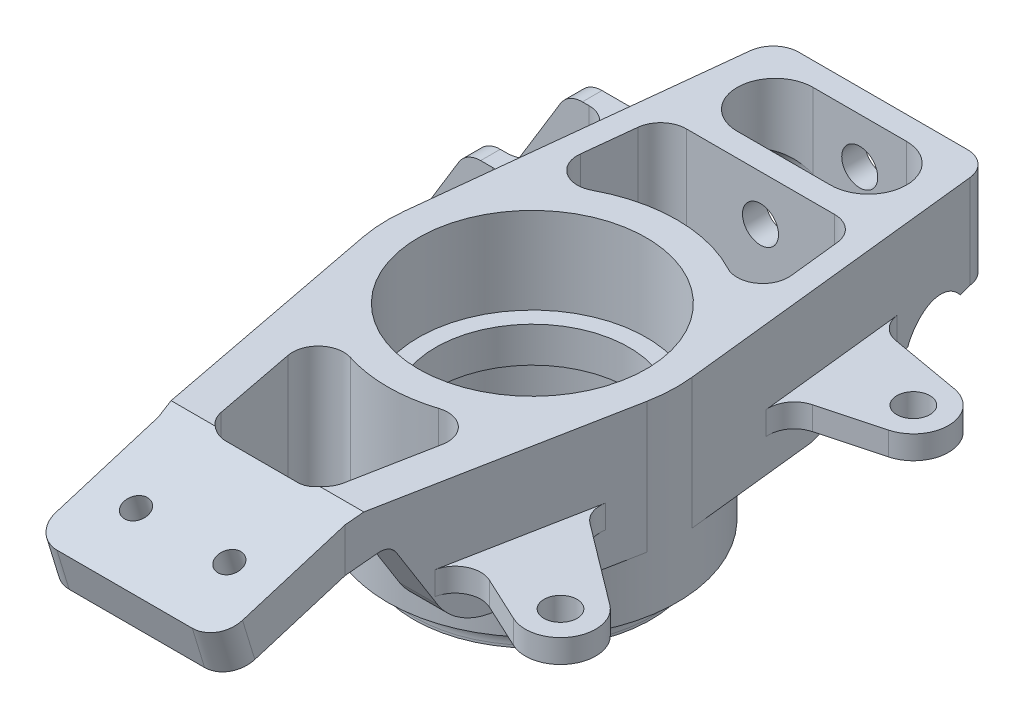
SolidWorks part; units mm, degrees
material "6061-T6 (SS)"
ref_plane "Front Plane" through (0, 0, 0) normal (0, 0, 1) x (1, 0, 0)
ref_plane "Top Plane" through (0, 0, 0) normal (0, 1, 0) x (1, 0, 0)
ref_plane "Right Plane" through (0, 0, 0) normal (1, 0, 0) x (0, 0, -1)
sketch "UBJ LBJ Geometry" plane through (0, 0, 0) normal (1, 0, 0) x (0, 0, -1)
  line L0 (0, 0) -> (0, -97.4059) construction
  line L1 (0, 0) -> (-30.7529, 0) construction
  line L2 (0, 22) -> (-45.5659, 22) construction
  line L3 (0, -10.5425) -> (-23.1063, -10.5425) construction
  line L4 (-84.7344, -51.66) -> (78.74, -22.958) construction
  line L5 (49.4563, 0) -> (49.4563, -88.2735) construction
  circle A0 centre (-84.7344, -51.66) radius 10.3251 construction
  circle A1 centre (78.74, -22.958) radius 10.3251 construction
  dimension "D7" = 20.6502
  dimension "D8" = 20.6502
  dimension "D1" = 22
  dimension "D2" = 32.5425
  dimension "D3" = 44.958
  dimension "D4" = 73.66
  dimension "D5" = 84.7344
  dimension "D6" = 78.74
  dimension "D9" = 29.2837
ref_plane "Wheel Face " through (0, 22, 0) normal (0, -1, 0) x (-1, 0, 0)
ref_plane "Upright Face" through (0, -10.5425, 0) normal (0, -1, 0) x (-1, 0, 0)
ref_plane "Tie Bracket Plane" through (0, 0, -49.4563) normal (0, 0, 1) x (1, 0, 0)
sketch "Tie Bracket Geometry" plane through (0, 0, -49.4563) normal (0, 0, 1) x (1, 0, 0)
  line L0 (0, -28.0995) -> (-60.5599, -51.7108) construction
  line L4 (0, 200000) -> (0, -200097.4059) construction
  circle A0 centre (-60.5599, -51.7108) radius 8.948 construction
  dimension "D1" = 65
  dimension "D2" = 68.7
sketch "Sketch1" plane through (0, 0, 0) normal (0, 0, 1) x (1, 0, 0)
  line L1 (-75.0953, -10.5425) -> (75.0953, -10.5425) construction
  line L2 (-39.37, -10.5425) -> (-39.37, -61.3425)
  line L3 (-39.37, -61.3425) -> (-32.258, -61.3425)
  line L4 (-32.258, -61.3425) -> (-32.258, -68.9625)
  line L5 (-32.258, -68.9625) -> (-30.9829, -68.9625)
  line L8 (-30.9829, -10.5425) -> (-30.9829, -34.0375)
  line L9 (-30.9829, -34.0375) -> (-26.289, -34.0375)
  line L10 (-26.289, -34.0375) -> (-26.289, -43.6895)
  line L11 (-26.289, -43.6895) -> (-30.9829, -43.6895)
  line L12 (-30.9829, -43.6895) -> (-30.9829, -68.9625)
  line L15 (-39.37, -10.5425) -> (-30.9829, -10.5425)
  line L17 (0, 0) -> (0, -23.5057) construction
  dimension "D1" = 9.652
  dimension "D2" = 61.9658
  dimension "D3" = 25.273
  dimension "D4" = 52.578
  dimension "D5" = 23.495
  dimension "D6" = 50.8
  dimension "D7" = 78.74
  dimension "D8" = 64.516
revolve "Bearing Housing Revolve" add sketch "Sketch1" angle 360 about L17
fillet "Bearing Housing Fillet" radius 6.985 1 edges at (0, -61.3425, 32.258)
sketch "Sketch2" plane through (0, -10.5425, 0) normal (0, -1, 0) x (-1, 0, 0)
  line L3 (39.37, -43.18) -> (39.37, 0)
  line L4 (-39.37, -43.18) -> (-39.37, 0)
  line L5 (39.37, -43.18) -> (-39.37, -43.18)
  circle A4 centre (0, 0) radius 39.37 construction
  arc A5 (39.37, 0) -> (-39.37, 0) centre (0, 0) cw
  dimension "D1" = 43.18
extrude "UBJ Prep" add sketch "Sketch2" along normal blind 35.56
sketch "Sketch3" plane through (-39.37, 0, 0) normal (-1, 0, 0) x (0, 0, 1)
  line L0 (-120.7672, 22) -> (120.7672, 22) construction
  line L1 (43.18, -10.5425) -> (72.0727, -10.5425)
  line L2 (72.0727, -10.5425) -> (110.937, -22.4245)
  line L3 (110.937, -22.4245) -> (107.5952, -33.355)
  line L4 (107.5952, -33.355) -> (68.7309, -21.473)
  line L6 (43.18, -46.1025) -> (43.18, -10.5425)
  line L7 (72.0727, -10.5425) -> (68.7309, -21.473) construction
  line L8 (104.3241, 12.415) -> (84.7344, -51.66) construction
  line L9 (55.2328, -39.1959) -> (64.6966, -23.0471)
  circle A0 centre (84.7344, -51.66) radius 12.7 construction
  arc A1 (43.18, -46.1025) -> (55.2328, -39.1959) centre (43.18, -32.1325) ccw
  arc A2 (68.7309, -21.473) -> (64.6966, -23.0471) centre (67.7098, -24.8129) ccw
  dimension "D7" = 6.985
  dimension "D8" = 27.94
  dimension "D9" = 25.4
  dimension "D1" = 73.66
  dimension "D2" = 84.7344
  dimension "D3" = 11.43
  dimension "D4" = 40.64
  dimension "D5" = 17
  dimension "D6" = 16.51
extrude "UBJ Extrude " add sketch "Sketch3" against normal up to surface (78.74 mm away) up to face at (39.37, -28.3225, 21.59)
sketch "Sketch4" plane through (0, -0.4206, -0.1286) normal (0, -0.9563, -0.2924) x (1, 0, 0)
  line L0 (0, 112.6458) -> (0, 27.8969) construction
  line L1 (39.37, 112.6458) -> (-39.37, 112.6458) construction
  line L3 (-12.7, 96.1358) -> (12.7, 96.1358) construction
  circle A0 centre (-12.7, 96.1358) radius 3.2639
  circle A1 centre (12.7, 96.1358) radius 3.2639
  point P8 (0, 96.1358)
  dimension "D2" = 6.5278
  dimension "D1" = 25.4
extrude "Camber Block Holes" cut sketch "Sketch4" against normal up to surface (11.43 mm away) up to face at (0, -16.4835, 91.5049)
sketch "Sketch5" plane through (0, -46.1025, 0) normal (0, -1, 0) x (1, 0, 0)
  line L0 (-25.4, 107.5952) -> (-25.4, 76.3532)
  line L1 (25.4, 110.937) -> (39.37, 110.937)
  line L2 (39.37, 107.5952) -> (-39.37, 107.5952) construction
  line L4 (-25.4, 76.3532) -> (-38.6608, 7.4393)
  line L5 (25.4, 107.5952) -> (25.4, 76.3532)
  line L6 (25.4, 76.3532) -> (38.6608, 7.4393)
  line L7 (-25.4, 107.5952) -> (-25.4, 110.937)
  line L8 (39.37, 110.937) -> (-39.37, 110.937) construction
  line L9 (25.4, 107.5952) -> (25.4, 110.937)
  line L10 (-25.4, 110.937) -> (-39.37, 110.937)
  line L11 (-39.37, 110.937) -> (-39.37, 0)
  line L12 (39.37, 110.937) -> (39.37, 0)
  line L13 (-15.5718, 73.66) -> (15.5718, 73.66)
  line L14 (-15.5718, 73.66) -> (-23.6959, 31.4404)
  line L15 (15.5718, 73.66) -> (23.6959, 31.4404)
  arc A0 (-39.37, 0) -> (-38.6608, 7.4393) centre (0, 0) cw
  circle A1 centre (0, 0) radius 39.37 construction
  arc A2 (39.37, 0) -> (-39.37, 0) centre (0, 0) ccw construction
  arc A3 (39.37, 0) -> (38.6608, 7.4393) centre (0, 0) ccw
  arc A4 (-23.6959, 31.4404) -> (23.6959, 31.4404) centre (0, 0) cw
  point P31 (0, 73.66)
  dimension "D1" = 25.4
  dimension "D2" = 10.16
  dimension "D3" = 31.242
  dimension "D4" = 73.66
extrude "Weight Saving" cut sketch "Sketch5" against normal through all
fillet "Fillet2" radius 6.985 4 edges at (23.6959, -28.3225, 31.4404) (-23.6959, -28.3225, 31.4404) (15.5718, -17.0039, 73.66) (-15.5718, -17.0039, 73.66)
sketch "Sketch6" plane through (0, -10.5425, 0) normal (0, -1, 0) x (-1, 0, 0)
  line L0 (-39.37, 0) -> (-39.37, 40.64)
  line L1 (-39.37, 40.64) -> (39.37, 40.64)
  line L2 (39.37, 40.64) -> (39.37, 0)
  circle A0 centre (0, 0) radius 39.37 construction
  arc A1 (-39.37, 0) -> (39.37, 0) centre (0, 0) cw
  dimension "D1" = 40.64
extrude "LBJ Prep" add sketch "Sketch6" along normal blind 35.56
sketch "Sketch8" plane through (-39.37, 0, 0) normal (-1, 0, 0) x (0, 0, 1)
  line L0 (-40.64, -10.5425) -> (-95.4151, -10.5425)
  line L1 (-95.4151, -10.5425) -> (-95.4151, -35.9425)
  line L2 (-95.4151, -35.9425) -> (-89.0651, -35.9425)
  line L7 (-40.64, -46.1025) -> (-40.64, -10.5425)
  line L8 (-120.7672, 22) -> (120.7672, 22) construction
  line L9 (-89.0651, -35.9425) -> (-89.0651, -10.5425) construction
  line L10 (-89.0651, -35.9425) -> (-40.64, -46.1025)
  circle A0 centre (-78.74, -22.958) radius 10.3251 construction
  dimension "D3" = 20.6502
  dimension "D1" = 78.74
  dimension "D2" = 44.958
  dimension "D4" = 6.35
  dimension "D5" = 25.4
extrude "LBJ Area " add sketch "Sketch8" against normal up to surface (78.74 mm away) up to face at (39.37, -28.3225, -20.32)
sketch "Sketch7" plane through (0, -46.1025, 0) normal (0, -1, 0) x (1, 0, 0)
  line L0 (-12.7, -78.74) -> (12.7, -78.74) construction
  line L1 (0, -200000) -> (0, 200045.5659) construction
  line L2 (-12.7, -68.4149) -> (12.7, -68.4149)
  line L3 (-12.7, -89.0651) -> (12.7, -89.0651)
  line L4 (-29.21, -95.4151) -> (-39.1385, -4.2631)
  line L5 (39.37, -95.4151) -> (-39.37, -95.4151) construction
  line L6 (29.21, -95.4151) -> (39.1385, -4.2631)
  line L7 (-29.21, -95.4151) -> (-39.37, -95.4151)
  line L8 (-39.37, -95.4151) -> (-39.37, 0)
  line L9 (29.21, -95.4151) -> (39.37, -95.4151)
  line L10 (39.37, -95.4151) -> (39.37, 0)
  line L13 (-26.455, -62.0649) -> (26.455, -62.0649)
  line L14 (26.455, -62.0649) -> (30.5043, -24.8895)
  line L15 (-26.455, -62.0649) -> (-30.5043, -24.8895)
  arc A0 (-12.7, -68.4149) -> (-12.7, -89.0651) centre (-12.7, -78.74) ccw
  arc A1 (12.7, -89.0651) -> (12.7, -68.4149) centre (12.7, -78.74) ccw
  circle A2 centre (0, 0) radius 39.37 construction
  arc A3 (-39.37, 0) -> (39.37, 0) centre (0, 0) ccw construction
  arc A4 (39.37, 0) -> (39.1385, -4.2631) centre (0, 0) cw
  arc A5 (-39.37, 0) -> (-39.1385, -4.2631) centre (0, 0) ccw
  arc A6 (-30.5043, -24.8895) -> (30.5043, -24.8895) centre (0, 0) ccw
  point P4 (0, -78.74)
  point P28 (0, -62.0649)
  dimension "D1" = 78.74
  dimension "D2" = 20.6502
  dimension "D3" = 25.4
  dimension "D4" = 10.16
  dimension "D5" = 6.35
  dimension "D6" = 6.35
extrude "LBJ Taper And Slot" cut sketch "Sketch7" against normal up to surface (35.56 mm away)
fillet "Fillet3" radius 6.985 4 edges at (26.455, -26.0749, -62.0649) (-26.455, -26.0749, -62.0649) (30.5043, -28.3225, -24.8895) (-30.5043, -28.3225, -24.8895)
extrude "LBJ Holes 3/8 Close Fit Hole" cut sketch "Sketch9" against normal up to surface (33.3502 mm away) up to face at (0, -26.0749, -62.0649)
sketch "Sketch9" plane through (0, 0, -95.4151) normal (0, 0, -1) x (-1, 0, 0)
  circle A0 centre (0, -22.958) radius 4.9022
  dimension "D2" = 9.8044
  dimension "D1" = 22.958
ref_plane "Brake Mounting Plane" through (0, -30.7025, 0) normal (0, 1, 0) x (1, 0, 0)
sketch "Sketch10" plane through (0, -30.7025, 0) normal (0, 1, 0) x (1, 0, 0)
  line L0 (87.9814, 0) -> (161.3053, 0) construction
  line L1 (0, 72.9505) -> (0, 47.1638) construction
  line L2 (55.6514, 48) -> (55.6514, -48) construction
  line L3 (58.1309, 38.7464) -> (36.0276, 32.8239)
  line L4 (39.1385, 4.2631) -> (29.21, 95.4151) construction
  line L5 (36.0276, 32.8239) -> (32.8776, 61.7434)
  line L6 (32.8776, 61.7434) -> (57.3149, 57.4345)
  line L7 (61.4168, -40.3491) -> (36.0119, -21.2051)
  line L8 (26.2237, -72.0727) -> (38.6608, -7.4393) construction
  line L9 (36.0119, -21.2051) -> (31.031, -47.0897)
  line L10 (31.031, -47.0897) -> (51.6027, -56.6824)
  circle A0 centre (55.6514, 48) radius 4.5
  circle A1 centre (55.6514, -48) radius 4.5
  arc A2 (51.6027, -56.6824) -> (61.4168, -40.3491) centre (55.6514, -48) ccw
  arc A3 (58.1309, 38.7464) -> (57.3149, 57.4345) centre (55.6514, 48) ccw
  point P7 (55.6514, 0)
  dimension "D2" = 9
  dimension "D3" = 5.08
  dimension "D4" = 5.08
  dimension "D1" = 96
  dimension "D5" = 55.6514
  dimension "D6" = 80
  dimension "D7" = 75
  dimension "D8" = 53
  dimension "D9" = 65
extrude "Brake Mounts" add sketch "Sketch10" against normal blind 6.35
fillet "Fillet4" radius 6.985 4 edges at (36.0119, -33.8775, 21.2051) (31.031, -33.8775, 47.0897) (36.0276, -33.8775, -32.8239) (32.8776, -33.8775, -61.7434)
sketch "Sketch17" plane through (0, -37.0525, 0) normal (0, -1, 0) x (1, 0, 0)
  line L1 (36.8349, 16.928) -> (29.3384, 55.8861) construction
  line L3 (32.3099, -66.9555) -> (36.6761, -26.8705) construction
  line L6 (57.3149, -57.4345) -> (38.0409, -60.833) construction
  line L12 (61.4168, 40.3491) -> (39.4904, 23.8263) construction
  circle A0 centre (40.1682, 38.2515) radius 4.7625
  circle A1 centre (41.7635, -47.6031) radius 4.7625
  dimension "D1" = 9.525
  dimension "D2" = 9.525
  dimension "D3" = 2.54
  dimension "D4" = 2.54
  dimension "D5" = 7.62
  dimension "D6" = 6.35
extrude "rotor Cut " [suppressed] cut sketch "Sketch17" against normal up to surface (6.35 mm away)
sketch "Sketch16" plane through (0, -46.1025, 0) normal (0, 1, 0) x (1, 0, 0)
  line L0 (-38.6345, 8.89) -> (-55.7371, 8.89)
  line L1 (-38.6608, -7.4393) -> (-26.2237, -72.0727) construction
  line L2 (-55.7371, 8.89) -> (-55.7371, -8.89)
  line L3 (-55.7371, -8.89) -> (-38.3816, -8.89)
  line L5 (-29.21, 95.4151) -> (-39.1385, 4.2631) construction
  line L6 (-38.6345, 8.89) -> (-38.3816, -8.89)
  circle A0 centre (-46.609, 0) radius 5.9531
  point P8 (-55.7371, 0)
  dimension "D1" = 3.175
  dimension "D3" = 11.9062
  dimension "D2" = 46.609
  dimension "D4" = 17.78
extrude "Speed Sensor Mount" add sketch "Sketch16" along normal blind 5.08
fillet "Speed Sensor Fillet" radius 6.985 4 edges at (-55.7371, -43.5625, 8.89) (-55.7371, -43.5625, -8.89) (-38.3816, -43.5625, 8.89) (-38.6345, -43.5625, -8.89)
thread "15/32-32" pitch 0.9071 method cut profile "Thread Profile1" start angle 0, offset 1, length 10, pitch 0.7937, diameter 11.9062
ref_plane "Plane1" through (-40.6559, -45.1025, 0) normal (0, 0, 1) x (1, 0, 0)
sketch "Thread Profile1" plane through (-40.6559, -45.1025, 0) normal (0, 0, 1) x (1, 0, 0)
  line L0 (0, 0) -> (0, 0.9071) construction
  line L1 (0, 0) -> (0.491, 0.2835)
  line L2 (0.491, 0.2835) -> (0.491, 0.3969)
  line L3 (0.491, 0.3969) -> (0, 0.6804)
  line L4 (0.491, 0.3402) -> (0, 0.3402) construction
  line L11 (0, 0) -> (0, 0.6804)
  point P2 (0, 0)
  dimension "Pitch" = 0.9071
  dimension "Profile_Angle" = 60
  dimension "Profile_Land" = 0.1134
  dimension "Profile_Height" = 0.491
sketch "Sketch12" plane through (0, 0, -49.4563) normal (0, 0, 1) x (1, 0, 0)
  line L0 (0, 3.2946) -> (0, -38.5659) construction
  line L1 (-90.5661, 0) -> (-38.2005, 0) construction
  line L2 (-68.726, -10.5425) -> (-68.726, -51.7108)
  line L3 (-52.3938, -10.5425) -> (-52.3938, -51.7108)
  line L4 (-68.726, -10.5425) -> (-52.3938, -10.5425)
  line L6 (-75.0953, -10.5425) -> (75.0953, -10.5425) construction
  circle A0 centre (-60.5599, -51.7108) radius 3.2639
  arc A1 (-68.726, -51.7108) -> (-52.3938, -51.7108) centre (-60.5599, -51.7108) ccw
  dimension "D1" = 6.5278
  dimension "D2" = 4.9022
extrude "Initial Toe Bracket" add sketch "Sketch12" along normal blind 16.51 and the other way blind 16.51 separate body
sketch "Sketch13" plane through (-52.3938, 0, 0) normal (1, 0, 0) x (0, 0, -1)
  line L0 (32.9463, -16.8925) -> (65.9663, -16.8925)
  line L1 (65.9663, -51.7108) -> (65.9663, -10.5425) construction
  line L2 (65.9663, -16.8925) -> (65.9663, -38.4825)
  line L3 (32.9463, -16.8925) -> (32.9463, -38.4825)
  line L4 (200000, -10.5425) -> (-200023.1063, -10.5425) construction
  line L5 (32.9463, -38.4825) -> (65.9663, -38.4825)
  line L6 (32.9463, -51.7108) -> (32.9463, -10.5425) construction
  dimension "D1" = 6.35
  dimension "D2" = 21.59
extrude "Toe Bracket Connection to Upright" add sketch "Sketch13" along normal up to surface (19.9762 mm away) up to face at (-34.7109, -33.4025, -44.9123)
sketch "Sketch14" plane through (0, 0, -65.9663) normal (0, 0, -1) x (-1, 0, 0)
  line L0 (52.3938, -16.8925) -> (68.726, -16.8925)
  line L1 (68.726, -10.5425) -> (68.726, -51.7108) construction
  line L2 (68.726, -16.8925) -> (68.726, -10.5425)
  line L3 (68.726, -10.5425) -> (52.3938, -10.5425)
  line L4 (52.3938, -10.5425) -> (52.3938, -16.8925)
extrude "Excess Toe Bracket Cut" cut sketch "Sketch14" against normal up to surface (33.02 mm away) up to face at (-52.382, -30.4278, -32.9463)
sketch "Sketch19" plane through (0, 0, -32.9463) normal (0, 0, 1) x (1, 0, 0)
  line L0 (-53.5754, -55.9418) -> (-42.9993, -38.4825)
  line L1 (-42.9993, -38.4825) -> (-52.3938, -38.4825)
  line L2 (-52.3938, -38.4825) -> (-53.5754, -55.9418)
  line L3 (-36.0143, -38.4825) -> (-52.3938, -38.4825) construction
  line L4 (-36.0143, -16.8925) -> (-36.0143, -38.4825) construction
  arc A0 (-68.726, -51.7108) -> (-52.3938, -51.7108) centre (-60.5599, -51.7108) ccw construction
  dimension "D1" = 6.985
extrude "Adding To Toe" add sketch "Sketch19" against normal up to surface (33.02 mm away) up to face at (-51.1792, -37.0563, -65.9663)
sketch "Sketch20" plane through (0, 0, -32.9463) normal (0, 0, 1) x (1, 0, 0)
  line L0 (-50.946, -16.8925) -> (-68.726, -16.8925)
  line L1 (-36.0143, -16.8925) -> (-68.726, -16.8925) construction
  line L2 (-68.726, -16.8925) -> (-68.726, -46.1025)
  line L3 (-68.726, -16.8925) -> (-68.726, -51.7108) construction
  line L4 (-68.726, -46.1025) -> (-50.946, -16.8925)
  dimension "D1" = 17.78
  dimension "D2" = 29.21
extrude "Cut-Extrude1" cut sketch "Sketch20" against normal up to surface (33.02 mm away) up to face at (-50.0779, -37.3587, -65.9663)
sketch "Sketch15" plane through (-68.726, 0, 0) normal (-1, 0, 0) x (0, 0, 1)
  line L0 (-60.6323, -16.8925) -> (-38.2803, -16.8925)
  line L1 (-38.2803, -16.8925) -> (-38.2803, -59.8769)
  line L2 (-65.9663, -59.8769) -> (-32.9463, -59.8769) construction
  line L3 (-38.2803, -59.8769) -> (-60.6323, -59.8769)
  line L4 (-60.6323, -59.8769) -> (-60.6323, -16.8925)
  line L6 (-49.4563, -25.7825) -> (-49.4563, -39.109) construction
  line L8 (-32.9463, -16.8925) -> (-65.9663, -16.8925) construction
  point P9 (-49.4563, -16.8925)
  point P11 (-49.4563, -16.8925)
  dimension "D1" = 22.352
extrude "Toe Bracket Slot" cut sketch "Sketch15" against normal blind 30.48
fillet "Toe Bracket Fillet" radius 6.985 2 edges at (-32.4176, -27.6875, -65.9663) (-36.0143, -27.6875, -32.9463)
fillet "Fillet7" radius 6.985 4 edges at (-68.726, -46.1025, -35.6133) (-68.726, -46.1025, -63.2993) (-50.946, -16.8925, -63.2993) (-50.946, -16.8925, -35.6133)
fillet "Inside Toe Fillet" radius 6.985 2 edges at (-38.246, -27.6875, -38.2803) (-38.246, -27.6875, -60.6323)
fillet "Outside Fillets" radius 6.985 4 edges at (-25.4, -27.8897, 109.2661) (25.4, -27.8897, 109.2661) (29.21, -23.2425, -95.4151) (-29.21, -23.2425, -95.4151)
sketch "Angle Reference" plane through (0, 0, -95.4151) normal (0, 0, -1) x (-1, 0, 0)
  line L0 (0, -22.958) -> (32.5253, -73.0426) construction
  line L1 (0, 0) -> (0, -88.2735) construction
  line L2 (0, -22.958) -> (69.6053, -82.0294) construction
  dimension "D1" = 33
  dimension "D2" = 16.68
ref_plane "Plane2" through (0, -22.958, -78.74) normal (-0.7624, -0.6471, 0) x (0, 0, 1)
sketch "Sketch22" plane through (0, -22.958, -78.74) normal (-0.7624, -0.6471, 0) x (0, 0, 1)
  line L0 (0, 2.032) -> (0, -5.588) construction
  line L3 (10.3251, 2.032) -> (10.3251, -5.588)
  line L4 (-10.3251, 2.032) -> (-10.3251, -5.588)
  arc A2 (10.3251, 2.032) -> (-10.3251, 2.032) centre (0, 2.032) ccw
  arc A3 (-10.3251, -5.588) -> (10.3251, -5.588) centre (0, -5.588) ccw
  point P2 (0, -1.778)
  dimension "D1" = 20.6502
  dimension "D2" = 2.032
  dimension "D3" = 7.62
extrude "Angle Slot Cut" cut sketch "Sketch22" along normal through all
mirror "Mirror1" about plane through (0, 0, 0) normal (1, 0, 0) of "Angle Slot Cut"
equation "\"Wheel_Offset\"= 22mm"
equation "\"HUB_to_UBJ_Lat\"= 2.9in"
equation "\"Hub_to_UBJ_Vert\"= 3.336in"
equation "\"Hub_to_LBJ_Lat\"= 1.77in"
equation "\"Hub_to_LBJ_Vert\"= 3.1in"
equation "\"Wheel_face_to_Upright_back\"= 1.2812in'This is the distance between the whee face to the upright back."
equation "\"UBJ_Angle\"= 17deg"
equation "\"D2@UBJ LBJ Geometry\" = \"Wheel_face_to_Upright_back\""
equation "\"D3@UBJ LBJ Geometry\" = \"Hub_to_LBJ_Lat\""
equation "\"D4@UBJ LBJ Geometry\" = \"HUB_to_UBJ_Lat\""
equation "\"D5@UBJ LBJ Geometry\" = \"Hub_to_UBJ_Vert\""
equation "\"D6@UBJ LBJ Geometry\" = \"Hub_to_LBJ_Vert\""
equation "\"D1@Sketch3\"=\"HUB_to_UBJ_Lat\""
equation "\"D2@Sketch3\"=\"Hub_to_UBJ_Vert\""
equation "\"D1@Sketch8\"=\"Hub_to_LBJ_Vert\""
equation "\"D2@Sketch8\"=\"Hub_to_LBJ_Lat\""
equation "\"Hub_Tie_Bracket_Vert\"= 2in'(Not Given) Ask Sus and Controls later"
equation "\"Tie_Beta\"= 21.3deg'From FE11 Master "
equation "\"Toe_Arm\"= 65mm'From FE11 Master (Assume Dist start at KPI)"
equation "\"D1@Sketch7\"=\"Hub_to_LBJ_Vert\""
equation "\"D1@Sketch9\"=\"Hub_to_LBJ_Lat\"-\"Wheel_Offset\""
equation "\"D1@Tie Bracket Geometry\" = \"Toe_Arm\""
equation "\"D2@Tie Bracket Geometry\" = 90 - \"Tie_Beta\""
equation "\"oranizeBlock\"= 0"
equation "\"BrakeAngle\"= 65deg"
equation "\"D5@Sketch3\"=\"UBJ_Angle\""
equation "\"D1@Sketch7\"=\"Hub_to_LBJ_Lat\""
